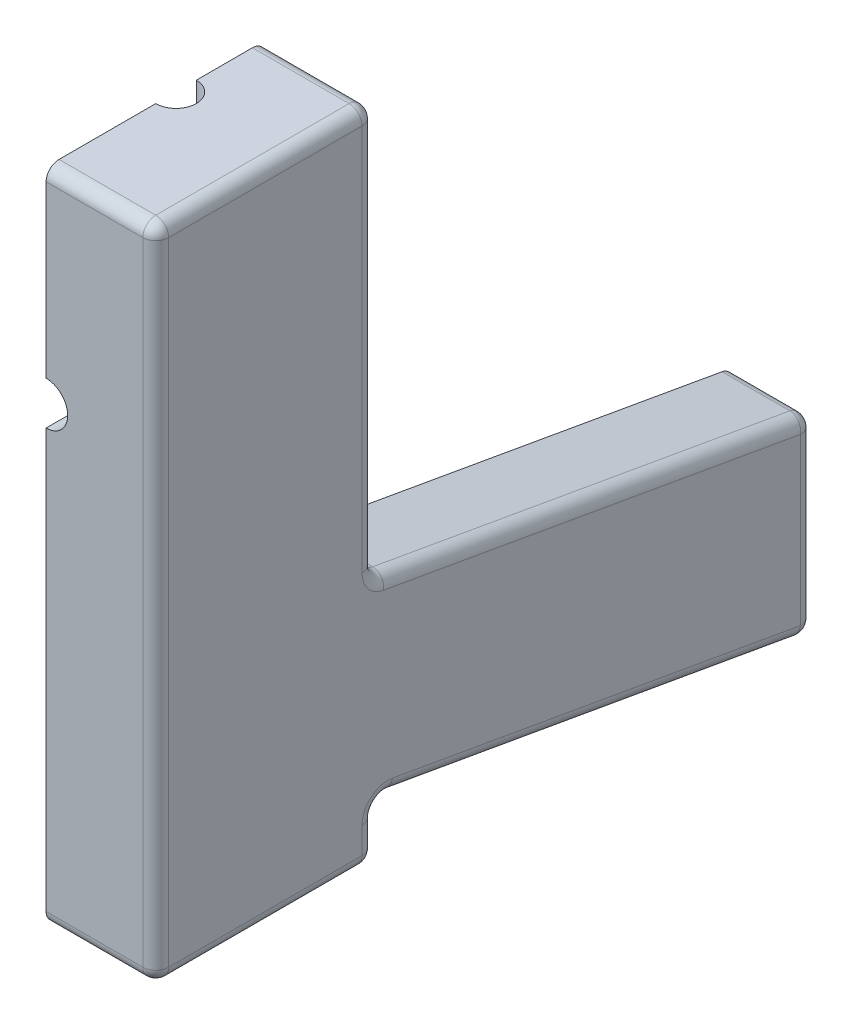
SolidWorks part; units mm, degrees
ref_plane "Front Plane" through (0, 0, 0) normal (0, 0, 1) x (1, 0, 0)
ref_plane "Top Plane" through (0, 0, 0) normal (0, 1, 0) x (1, 0, 0)
ref_plane "Right Plane" through (0, 0, 0) normal (1, 0, 0) x (0, 0, -1)
sketch "Sketch1" plane through (0, 0, 0) normal (0, 1, 0) x (1, 0, 0)
  line L1 (0, 0) -> (25.4, 0)
  line L2 (0, 0) -> (0, 50.8)
  line L3 (0, 50.8) -> (25.4, 50.8)
  line L4 (25.4, 0) -> (25.4, 50.8)
  dimension "D1" = 25.4
  dimension "D2" = 50.8
extrude "Boss-Extrude1" add sketch "Sketch1" along normal blind 152.4
sketch "Sketch2" plane through (0, 0, 0) normal (-1, 0, 0) x (0, 0, 1)
  line L0 (0, 152.4) -> (0, 0) construction
  line L1 (-6.35, 146.05) -> (-44.45, 146.05)
  line L2 (-6.35, 146.05) -> (-6.35, 6.35)
  line L3 (-6.35, 6.35) -> (-44.45, 6.35)
  line L4 (-44.45, 146.05) -> (-44.45, 6.35)
  line L5 (-50.8, 152.4) -> (0, 152.4) construction
  line L6 (-50.8, 152.4) -> (-50.8, 0) construction
  line L7 (-50.8, 0) -> (0, 0) construction
  dimension "D1" = 6.35
  dimension "D2" = 6.35
  dimension "D3" = 6.35
  dimension "D4" = 6.35
extrude "Cut-Extrude1" cut sketch "Sketch2" against normal blind 19.05
sketch "Sketch3" plane through (0, 0, 0) normal (0, 0, 1) x (1, 0, 0)
  line L0 (0, 152.4) -> (0, 0) construction
  line L1 (0, 110) -> (0, 100)
  arc A0 (0, 110) -> (0, 100) centre (0, 105) cw
  dimension "D1" = 100
extrude "HitLED" cut sketch "Sketch3" against normal up to next
sketch "Sketch5" plane through (0, 146.05, 0) normal (0, -1, 0) x (1, 0, 0)
  line L0 (0, -6.35) -> (0, -44.45) construction
  line L1 (0, -25.4) -> (0, -34.8)
  arc A0 (0, -25.4) -> (0, -34.8) centre (0, -30.1) cw
extrude "IRLED" cut sketch "Sketch5" against normal up to next
sketch "Sketch6" plane through (19.05, 0, 0) normal (-1, 0, 0) x (0, 0, 1)
  line L0 (-33.53, 146.05) -> (-33.53, 44.45)
  line L1 (-27.18, 146.05) -> (-41.45, 146.05)
  line L2 (-27.18, 146.05) -> (-27.18, 44.45)
  line L3 (-27.18, 44.45) -> (-41.45, 44.45)
  line L4 (-41.45, 146.05) -> (-41.45, 44.45)
  line L5 (-35.1, 44.45) -> (-35.1, 146.05)
  line L7 (-6.35, 146.05) -> (-44.45, 146.05) construction
  line L8 (-44.45, 146.05) -> (-44.45, 6.35) construction
  line M8 (-6.35, 146.05) -> (-44.45, 146.05)
  dimension "D1" = 0
  dimension "D2" = 3
  dimension "D3" = 1.57
  dimension "D4" = 6.35
  dimension "D5" = 6.35
  dimension "D6" = 101.6
extrude "Boss-Extrude2" add sketch "Sketch6" along normal blind 6.35 contours L3 L2 L0 M8 | L3 L5 L1 L4 region at (19.05, 95.25, -30.355) region at (19.05, 95.25, -38.275)
sketch "Sketch13" plane through (25.4, 0, -25.4) normal (-1, 0, 0) x (0, 0, 1)
  line L4 (-25.4, 57.15) -> (-25.4, 12.7)
  line L5 (-25.4, 12.7) -> (-127, -5.2148)
  line L6 (-127, -5.2148) -> (-127, 39.2352)
  line L7 (-127, 39.2352) -> (-25.4, 57.15)
  point P0 (0, 0)
  dimension "D2" = 12.7
extrude "Butt" add sketch "Sketch13" along normal blind 18.7188
fillet "Fillet1" radius 3 16 edges at (16.0406, 12.7, -50.8) (16.0406, -5.2148, -152.4) (16.0406, 39.2352, -152.4) (16.0406, 57.15, -50.8) (12.7, 152.4, -50.8) (12.7, 152.4, 0) (25.4, 152.4, -25.4) (25.4, 104.775, -50.8) (25.4, 48.1926, -101.6) (25.4, 17.0102, -152.4) (25.4, 3.7426, -101.6) (25.4, 6.35, -50.8) (12.7, 0, -50.8) (12.7, 0, 0) (25.4, 0, -25.4) (25.4, 76.2, 0)
